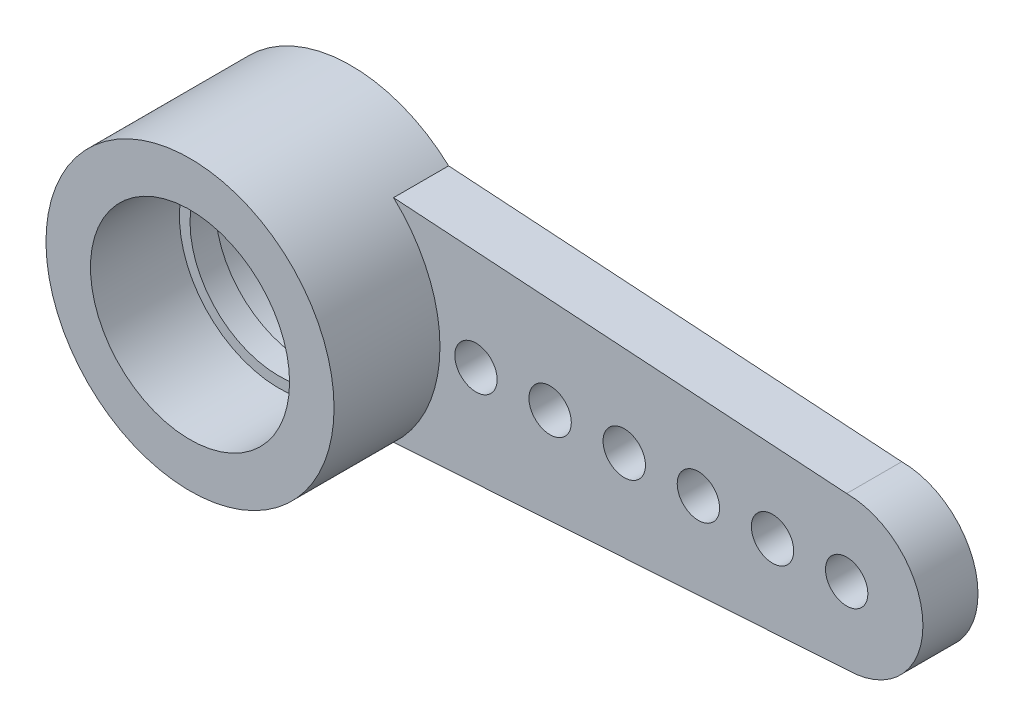
SolidWorks part; units mm, degrees
ref_plane "Front Plane" through (0, 0, 0) normal (0, 0, 1) x (1, 0, 0)
ref_plane "Top Plane" through (0, 0, 0) normal (0, 1, 0) x (1, 0, 0)
ref_plane "Right Plane" through (0, 0, 0) normal (1, 0, 0) x (0, 0, -1)
sketch "Sketch1" plane through (0, 0, 0) normal (0, 0, 1) x (1, 0, 0)
  line L0 (0, 0) -> (11.2, 0) construction
  line L1 (0, 0) -> (0, 1.8761) construction
  line L2 (13, 1.8) -> (2.3043, 2.5)
  line L3 (13, -1.8) -> (2.3043, -2.5)
  arc A0 (2.3043, 2.5) -> (2.3043, -2.5) centre (0, 0) ccw
  arc A1 (13, -1.8) -> (13, 1.8) centre (13, 0) ccw
  dimension "D1" = 13
  dimension "D2" = 6.8
  dimension "D3" = 3.6
  dimension "D4" = 5
extrude "Boss-Extrude1" add sketch "Sketch1" along normal blind 1.3
sketch "Sketch2" plane through (0, 0, 1.3) normal (0, 0, 1) x (1, 0, 0)
  circle A0 centre (0, 0) radius 2.35
  dimension "D1" = 4.7
extrude "Cut-Extrude1" cut sketch "Sketch2" against normal up to surface (1.3 mm away) up to face at (6.6761, 0, 0)
sketch "Sketch3" plane through (0, 0, 1.3) normal (0, 0, 1) x (1, 0, 0)
  circle A0 centre (0, 0) radius 3.4
  arc A1 (2.3043, 2.5) -> (2.3043, -2.5) centre (0, 0) ccw construction
  circle A2 centre (0, 0) radius 2.35
extrude "Boss-Extrude2" add sketch "Sketch3" along normal blind 2.5
sketch "Sketch4" plane through (0, 0, 0) normal (0, 0, -1) x (-1, 0, 0)
  circle A0 centre (0, 0) radius 2.35 construction
  circle A1 centre (0, 0) radius 2.35
  circle A2 centre (0, 0) radius 2.1
  dimension "D1" = 4.2
extrude "Boss-Extrude3" add sketch "Sketch4" against normal offset from surface (0.6 mm away) 2.1 from offset 1.1 up to face at (3.4, 0, 3.8) offset against normal yes
sketch "Sketch5" plane through (0, 0, 0) normal (0, 0, -1) x (-1, 0, 0)
  circle A0 centre (-13, 0) radius 0.5
  circle A1 centre (-11.25, 0) radius 0.5
  circle A2 centre (-9.5, 0) radius 0.5
  circle A3 centre (-7.75, 0) radius 0.5
  circle A4 centre (-6, 0) radius 0.5
  circle A5 centre (-4.25, 0) radius 0.5
  dimension "D1" = 1
  dimension "D2" = 6
extrude "Cut-Extrude3" cut sketch "Sketch5" against normal up to next
